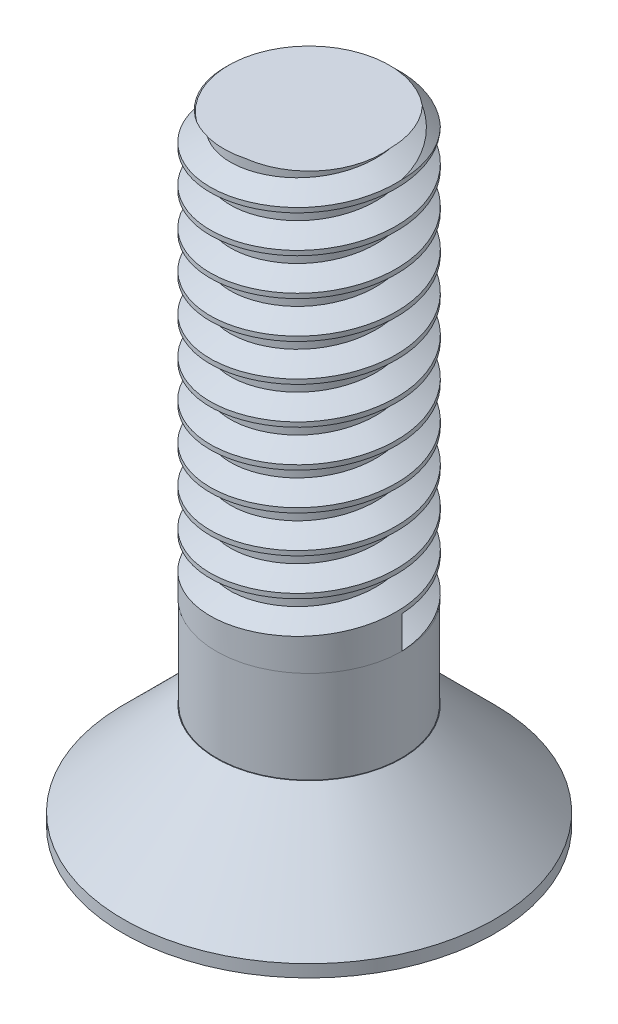
SolidWorks part; units mm, degrees
material "Galvanized Steel"
ref_plane "Front Plane" through (0, 0, 0) normal (0, 0, 1) x (1, 0, 0)
ref_plane "Top Plane" through (0, 0, 0) normal (0, 1, 0) x (1, 0, 0)
ref_plane "Right Plane" through (0, 0, 0) normal (1, 0, 0) x (0, 0, -1)
sketch "Sketch1" plane through (0, 0, 0) normal (0, 0, 1) x (1, 0, 0)
  line L0 (0, 0) -> (0, 13.3573) construction
  line L1 (0, -1.8739) -> (-3, -1.8739)
  line L2 (-3, -1.8739) -> (-3, -1.6739)
  line L3 (-1.5, 8.1261) -> (0, 8.1261)
  line L4 (-1.5, 1.3261) -> (-1.5, 8.1261)
  line L5 (-3, -1.6739) -> (-1.5, -0.1739)
  line L7 (0, -1.8739) -> (0, 8.1261)
  line L8 (-1.5, 1.3261) -> (-1.49, 1.3261)
  line L10 (-1.5, -0.1739) -> (-1.49, -0.1739)
  line L18 (-1.49, -0.1739) -> (-1.49, 1.3261)
  point P9 (-1.5, 9.9261)
  point P12 (-1.49, 3.622)
  point P13 (-1.49, 9.9161)
  point P16 (0, 3.6361)
  dimension "dk" = 6
  dimension "c" = 0.2
  dimension "k" = 1.7
  dimension "d" = 3
  dimension "l" = 10
  dimension "lg" = 3.2
revolve "Revolve1" add sketch "Sketch1" angle 360 about L0
chamfer "Chamfer1" distance 0.2 angle 45 1 edges at (0, 8.1261, -1.5)
sketch "Sketch2" plane through (0, -1.8739, 0) normal (0, -1, 0) x (1, 0, 0)
  line L1 (1.1547, 0) -> (0.5774, 1)
  line L2 (0.5774, 1) -> (-0.5774, 1)
  line L3 (-0.5774, 1) -> (-1.1547, 0)
  line L4 (-1.1547, 0) -> (-0.5774, -1)
  line L5 (-0.5774, -1) -> (0.5774, -1)
  line L6 (0.5774, -1) -> (1.1547, 0)
  circle A0 centre (0, 0) radius 1 construction
  dimension "s" = 2
extrude "hex depth" cut sketch "Sketch2" against normal blind 1.2
sketch "Sketch3" plane through (0, -1.8739, 0) normal (0, -1, 0) x (1, 0, 0)
  circle A0 centre (0, 0) radius 1.1547
ref_plane "Plane1" through (0, -1.6739, 0) normal (0, 1, 0) x (1, 0, 0)
sketch "Sketch4" plane through (0, -1.6739, 0) normal (0, 1, 0) x (1, 0, 0)
  line L0 (-0.5774, -1) -> (-1.1547, 0) construction
  circle A0 centre (0, 0) radius 1
loft "hex corner cut" cut profiles "Sketch4", "Sketch3" connector at (-0.0697, -1.6739, 0.9976) connector at (0.0073, -1.8739, 1.1547)
thread "thread M3" pitch 0.6 method cut profile "Thread Profile2" start angle 0, offset 0, length 0, pitch 0.6, diameter 3
ref_plane "Plane3" through (1.5, 1.3261, 0) normal (0, 0, 1) x (1, 0, 0)
sketch "Thread Profile2" plane through (1.5, 1.3261, 0) normal (0, 0, 1) x (1, 0, 0)
  line L0 (0, 0) -> (0, 0.6) construction
  line L11 (0, 0) -> (0, 0.525)
  line L12 (0, 0.525) -> (-0.3248, 0.3375)
  line L13 (-0.3248, 0.3375) -> (-0.3248, 0.1875)
  line L15 (-0.3248, 0.1875) -> (0, 0)
  line L17 (-0.3248, 0.2625) -> (0, 0.2625) construction
  point P2 (0, 0)
  dimension "Pitch" = 0.6
  dimension "Profile_Angle" = 60
  dimension "Profile_Land" = 0.15
  dimension "Profile_Height" = 0.3248
thread "Thread M4" [suppressed] pitch 0.7 start angle 0, offset 0.01, length 0, pitch 0.7, diameter 4
ref_plane "Plane4" through (2, 19.1361, 0) normal (0, 0, 1) x (1, 0, 0)
sketch "Thread Profile3" plane through (2, 19.1361, 0) normal (0, 0, 1) x (1, 0, 0)
  line L0 (0, 0) -> (0, 0.7) construction
  line L11 (0, 0) -> (0, 0.6125)
  line L12 (0, 0.6125) -> (-0.3789, 0.3937)
  line L13 (-0.3789, 0.3937) -> (-0.3789, 0.2187)
  line L15 (-0.3789, 0.2187) -> (0, 0)
  line L17 (-0.3789, 0.3062) -> (0, 0.3062) construction
  point P2 (0, 0)
  dimension "Pitch" = 0.7
  dimension "Profile_Angle" = 60
  dimension "Profile_Land" = 0.175
  dimension "Profile_Height" = 0.3789
thread "Thread M5" [suppressed] pitch 0.8 start angle 0, offset 0.01, length 0, pitch 0.8, diameter 5
ref_plane "Plane5" through (2.5, 32.1361, 0) normal (0, 0, 1) x (1, 0, 0)
sketch "Thread Profile4" plane through (2.5, 32.1361, 0) normal (0, 0, 1) x (1, 0, 0)
  line L0 (0, 0) -> (0, 0.8) construction
  line L11 (0, 0) -> (0, 0.7)
  line L12 (0, 0.7) -> (-0.433, 0.45)
  line L13 (-0.433, 0.45) -> (-0.433, 0.25)
  line L15 (-0.433, 0.25) -> (0, 0)
  line L17 (-0.433, 0.35) -> (0, 0.35) construction
  point P2 (0, 0)
  dimension "Pitch" = 0.8
  dimension "Profile_Angle" = 60
  dimension "Profile_Land" = 0.2
  dimension "Profile_Height" = 0.433
thread "Thread M6" [suppressed] pitch 1 start angle 0, offset 0.1, length 0, pitch 1, diameter 6
ref_plane "Plane8" through (3, 4.5261, 0) normal (0, 0, 1) x (1, 0, 0)
sketch "Thread Profile7" plane through (3, 4.5261, 0) normal (0, 0, 1) x (1, 0, 0)
  line L0 (0, 0) -> (0, 1) construction
  line L11 (0, 0) -> (0, 0.875)
  line L12 (0, 0.875) -> (-0.5413, 0.5625)
  line L13 (-0.5413, 0.5625) -> (-0.5413, 0.3125)
  line L15 (-0.5413, 0.3125) -> (0, 0)
  line L17 (-0.5413, 0.4375) -> (0, 0.4375) construction
  point P2 (0, 0)
  dimension "Pitch" = 1
  dimension "Profile_Angle" = 60
  dimension "Profile_Land" = 0.25
  dimension "Profile_Height" = 0.5413
thread "Thread M8" [suppressed] pitch 1.25 start angle 0, offset 0.1, length 0, pitch 1.25, diameter 8
ref_plane "Plane6" through (4, 6.4261, 0) normal (0, 0, 1) x (1, 0, 0)
sketch "Thread Profile5" plane through (4, 6.4261, 0) normal (0, 0, 1) x (1, 0, 0)
  line L0 (0, 0) -> (0, 1.25) construction
  line L11 (0, 0) -> (0, 1.0937)
  line L12 (0, 1.0937) -> (-0.6766, 0.7031)
  line L13 (-0.6766, 0.7031) -> (-0.6766, 0.3906)
  line L15 (-0.6766, 0.3906) -> (0, 0)
  line L17 (-0.6766, 0.5469) -> (0, 0.5469) construction
  point P2 (0, 0)
  dimension "Pitch" = 1.25
  dimension "Profile_Angle" = 60
  dimension "Profile_Land" = 0.3125
  dimension "Profile_Height" = 0.6766
thread "Thread M10" [suppressed] pitch 1.5 start angle 0, offset 0.1, length 0, pitch 1.5, diameter 10
ref_plane "Plane7" through (5, 3.8261, 0) normal (0, 0, 1) x (1, 0, 0)
sketch "Thread Profile6" plane through (5, 3.8261, 0) normal (0, 0, 1) x (1, 0, 0)
  line L0 (0, 0) -> (0, 1.5) construction
  line L11 (0, 0) -> (0, 1.3125)
  line L12 (0, 1.3125) -> (-0.8119, 0.8437)
  line L13 (-0.8119, 0.8437) -> (-0.8119, 0.4687)
  line L15 (-0.8119, 0.4687) -> (0, 0)
  line L17 (-0.8119, 0.6562) -> (0, 0.6562) construction
  point P2 (0, 0)
  dimension "Pitch" = 1.5
  dimension "Profile_Angle" = 60
  dimension "Profile_Land" = 0.375
  dimension "Profile_Height" = 0.8119
thread "Thread M12" [suppressed] pitch 1.75 start angle 0, offset 0.1, length 0, pitch 1.75, diameter 12
ref_plane "Plane9" through (6, 10.0261, 0) normal (0, 0, 1) x (1, 0, 0)
sketch "Thread Profile8" plane through (6, 10.0261, 0) normal (0, 0, 1) x (1, 0, 0)
  line L0 (0, 0) -> (0, 1.75) construction
  line L11 (0, 0) -> (0, 1.5312)
  line L12 (0, 1.5312) -> (-0.9472, 0.9844)
  line L13 (-0.9472, 0.9844) -> (-0.9472, 0.5469)
  line L15 (-0.9472, 0.5469) -> (0, 0)
  line L17 (-0.9472, 0.7656) -> (0, 0.7656) construction
  point P2 (0, 0)
  dimension "Pitch" = 1.75
  dimension "Profile_Angle" = 60
  dimension "Profile_Land" = 0.4375
  dimension "Profile_Height" = 0.9472
thread "Thread M14" [suppressed] pitch 2 start angle 0, offset 0.1, length 0, pitch 2, diameter 14
ref_plane "Plane10" through (7, 11.2261, 0) normal (0, 0, 1) x (1, 0, 0)
sketch "Thread Profile9" plane through (7, 11.2261, 0) normal (0, 0, 1) x (1, 0, 0)
  line L0 (0, 0) -> (0, 2) construction
  line L11 (0, 0) -> (0, 1.75)
  line L12 (0, 1.75) -> (-1.0825, 1.125)
  line L13 (-1.0825, 1.125) -> (-1.0825, 0.625)
  line L15 (-1.0825, 0.625) -> (0, 0)
  line L17 (-1.0825, 0.875) -> (0, 0.875) construction
  point P2 (0, 0)
  dimension "Pitch" = 2
  dimension "Profile_Angle" = 60
  dimension "Profile_Land" = 0.5
  dimension "Profile_Height" = 1.0825
thread "Thread M16" [suppressed] pitch 2 start angle 0, offset 0.1, length 0, pitch 2, diameter 16
ref_plane "Plane11" through (8, 11.7261, 0) normal (0, 0, 1) x (1, 0, 0)
sketch "Thread Profile10" plane through (8, 11.7261, 0) normal (0, 0, 1) x (1, 0, 0)
  line L0 (0, 0) -> (0, 2) construction
  line L11 (0, 0) -> (0, 1.75)
  line L12 (0, 1.75) -> (-1.0825, 1.125)
  line L13 (-1.0825, 1.125) -> (-1.0825, 0.625)
  line L15 (-1.0825, 0.625) -> (0, 0)
  line L17 (-1.0825, 0.875) -> (0, 0.875) construction
  point P2 (0, 0)
  dimension "Pitch" = 2
  dimension "Profile_Angle" = 60
  dimension "Profile_Land" = 0.5
  dimension "Profile_Height" = 1.0825
thread "Thread M18" [suppressed] pitch 2.5 start angle 0, offset 0.1, length 0, pitch 2.5, diameter 18
ref_plane "Plane12" through (9, 13.7261, 0) normal (0, 0, 1) x (1, 0, 0)
sketch "Thread Profile11" plane through (9, 13.7261, 0) normal (0, 0, 1) x (1, 0, 0)
  line L0 (0, 0) -> (0, 2.5) construction
  line L11 (0, 0) -> (0, 2.1875)
  line L12 (0, 2.1875) -> (-1.3532, 1.4062)
  line L13 (-1.3532, 1.4062) -> (-1.3532, 0.7812)
  line L15 (-1.3532, 0.7812) -> (0, 0)
  line L17 (-1.3532, 1.0937) -> (0, 1.0937) construction
  point P2 (0, 0)
  dimension "Pitch" = 2.5
  dimension "Profile_Angle" = 60
  dimension "Profile_Land" = 0.625
  dimension "Profile_Height" = 1.3532
thread "Thread M20" [suppressed] pitch 2.5 start angle 0, offset 0.1, length 0, pitch 2.5, diameter 20
ref_plane "Plane13" through (10, 6.8261, 0) normal (0, 0, 1) x (1, 0, 0)
sketch "Thread Profile12" plane through (10, 6.8261, 0) normal (0, 0, 1) x (1, 0, 0)
  line L0 (0, 0) -> (0, 2.5) construction
  line L11 (0, 0) -> (0, 2.1875)
  line L12 (0, 2.1875) -> (-1.3532, 1.4062)
  line L13 (-1.3532, 1.4062) -> (-1.3532, 0.7812)
  line L15 (-1.3532, 0.7812) -> (0, 0)
  line L17 (-1.3532, 1.0937) -> (0, 1.0937) construction
  point P2 (0, 0)
  dimension "Pitch" = 2.5
  dimension "Profile_Angle" = 60
  dimension "Profile_Land" = 0.625
  dimension "Profile_Height" = 1.3532
thread "Thread M22" [suppressed] pitch 2.5 start angle 0, offset 0.1, length 0, pitch 2.5, diameter 22
ref_plane "Plane14" through (11, 18.8261, 0) normal (0, 0, 1) x (1, 0, 0)
sketch "Thread Profile13" plane through (11, 18.8261, 0) normal (0, 0, 1) x (1, 0, 0)
  line L0 (0, 0) -> (0, 2.5) construction
  line L11 (0, 0) -> (0, 2.1875)
  line L12 (0, 2.1875) -> (-1.3532, 1.4062)
  line L13 (-1.3532, 1.4062) -> (-1.3532, 0.7812)
  line L15 (-1.3532, 0.7812) -> (0, 0)
  line L17 (-1.3532, 1.0937) -> (0, 1.0937) construction
  point P2 (0, 0)
  dimension "Pitch" = 2.5
  dimension "Profile_Angle" = 60
  dimension "Profile_Land" = 0.625
  dimension "Profile_Height" = 1.3532
thread "Thread M24" [suppressed] pitch 3 start angle 0, offset 0.1, length 0, pitch 3, diameter 24
ref_plane "Plane15" through (12, 12.3261, 0) normal (0, 0, 1) x (1, 0, 0)
sketch "Thread Profile14" plane through (12, 12.3261, 0) normal (0, 0, 1) x (1, 0, 0)
  line L0 (0, 0) -> (0, 3) construction
  line L11 (0, 0) -> (0, 2.625)
  line L12 (0, 2.625) -> (-1.6238, 1.6875)
  line L13 (-1.6238, 1.6875) -> (-1.6238, 0.9375)
  line L15 (-1.6238, 0.9375) -> (0, 0)
  line L17 (-1.6238, 1.3125) -> (0, 1.3125) construction
  point P2 (0, 0)
  dimension "Pitch" = 3
  dimension "Profile_Angle" = 60
  dimension "Profile_Land" = 0.75
  dimension "Profile_Height" = 1.6238
